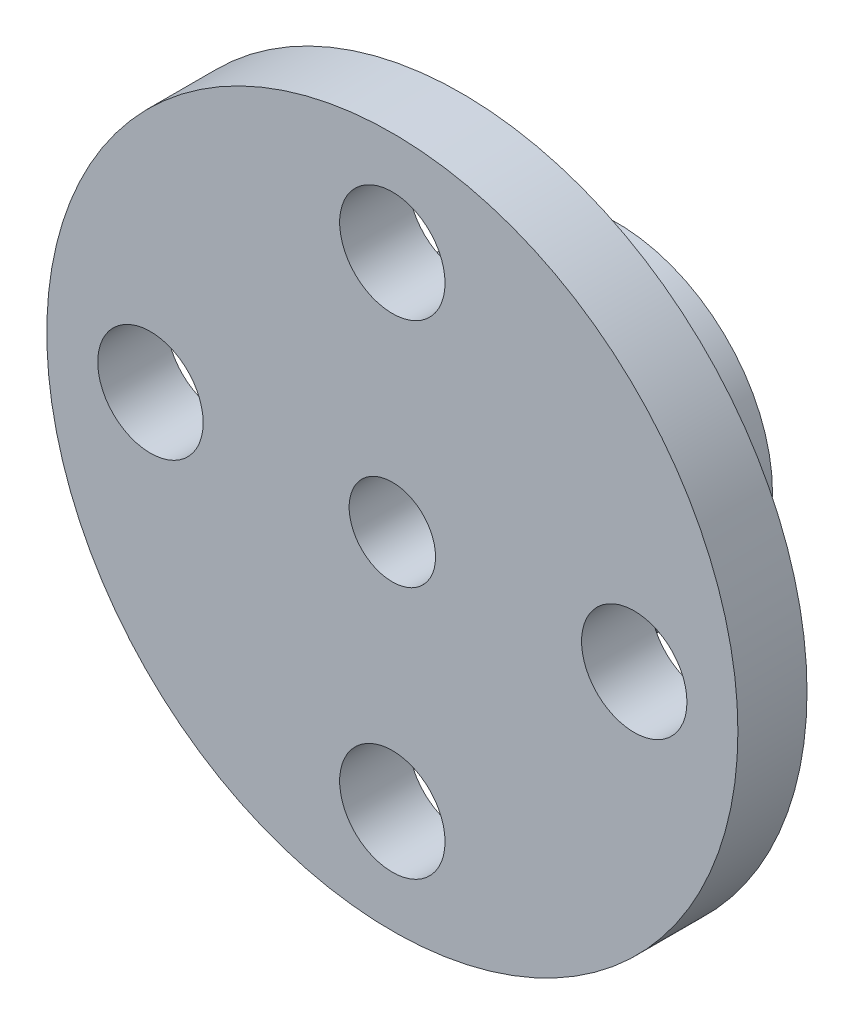
SolidWorks part; units mm, degrees
ref_plane "Front Plane" through (0, 0, 0) normal (0, 0, 1) x (1, 0, 0)
ref_plane "Top Plane" through (0, 0, 0) normal (0, 1, 0) x (1, 0, 0)
ref_plane "Right Plane" through (0, 0, 0) normal (1, 0, 0) x (0, 0, -1)
sketch "Sketch1" plane through (0, 0, 7) normal (0, 0, 1) x (1, 0, 0)
  line L0 (-1.3378, 2.3147) -> (-1.7435, 2.5633)
  line L1 (-1.8991, 2.4502) -> (-1.788, 1.9876)
  line L2 (-1.8714, 1.9093) -> (-2.3261, 2.0492)
  line L3 (-2.4487, 1.901) -> (-2.2261, 1.4805)
  line L4 (-2.2874, 1.3839) -> (-2.7627, 1.4063)
  line L5 (-2.8446, 1.2323) -> (-2.5244, 0.8804)
  line L6 (-2.5597, 0.7715) -> (-3.0256, 0.6751)
  line L7 (-3.0616, 0.4861) -> (-2.664, 0.2249)
  line L8 (-2.6712, 0.1107) -> (-3.0984, -0.0986)
  line L9 (-3.0864, -0.2905) -> (-2.6362, -0.4446)
  line L10 (-2.6148, -0.5571) -> (-2.9766, -0.866)
  line L11 (-2.9171, -1.0489) -> (-2.4428, -1.0863)
  line L12 (-2.3941, -1.1898) -> (-2.6677, -1.5791)
  line L13 (-2.5646, -1.7415) -> (-2.0959, -1.6597)
  line L14 (-2.023, -1.7478) -> (-2.1912, -2.1929)
  line L15 (-2.051, -2.3245) -> (-1.6174, -2.1288)
  line L16 (-1.5248, -2.196) -> (-1.577, -2.6689)
  line L17 (-1.4085, -2.7616) -> (-1.0371, -2.4641)
  line L18 (-0.9307, -2.5062) -> (-0.8637, -2.9772)
  line L19 (-0.6774, -3.0251) -> (-0.3918, -2.6446)
  line L20 (-0.2782, -2.659) -> (-0.0962, -3.0985)
  line L21 (0.0962, -3.0985) -> (0.2782, -2.659)
  line L22 (0.3918, -2.6446) -> (0.6774, -3.0251)
  line L23 (0.8637, -2.9772) -> (0.9307, -2.5062)
  line L24 (1.0371, -2.4641) -> (1.4085, -2.7616)
  line L25 (1.577, -2.6689) -> (1.5248, -2.196)
  line L26 (1.6174, -2.1288) -> (2.051, -2.3245)
  line L27 (2.1912, -2.1929) -> (2.023, -1.7478)
  line L28 (2.0959, -1.6597) -> (2.5646, -1.7415)
  line L29 (2.6677, -1.5791) -> (2.3941, -1.1898)
  line L30 (2.4428, -1.0863) -> (2.9171, -1.0489)
  line L31 (2.9766, -0.866) -> (2.6148, -0.5571)
  line L32 (2.6362, -0.4446) -> (3.0864, -0.2905)
  line L33 (3.0984, -0.0986) -> (2.6712, 0.1107)
  line L34 (2.664, 0.2249) -> (3.0616, 0.4861)
  line L35 (3.0256, 0.6751) -> (2.5597, 0.7715)
  line L36 (2.5244, 0.8804) -> (2.8446, 1.2323)
  line L37 (2.7627, 1.4063) -> (2.2874, 1.3839)
  line L38 (2.2261, 1.4805) -> (2.4487, 1.901)
  line L39 (2.3261, 2.0492) -> (1.8714, 1.9093)
  line L40 (1.788, 1.9876) -> (1.8991, 2.4502)
  line L41 (1.7435, 2.5633) -> (1.3378, 2.3147)
  line L42 (1.2375, 2.3698) -> (1.23, 2.8455)
  line L43 (1.0512, 2.9163) -> (0.7201, 2.5747)
  line L44 (0.6093, 2.6031) -> (0.4837, 3.062)
  line L45 (0.2929, 3.0861) -> (0.0572, 2.6729)
  line L46 (-0.0572, 2.6729) -> (-0.2929, 3.0861)
  line L47 (-0.4837, 3.062) -> (-0.6093, 2.6031)
  line L48 (-0.7201, 2.5747) -> (-1.0512, 2.9163)
  line L49 (-1.23, 2.8455) -> (-1.2375, 2.3698)
  line L150 (-1.8428, 2.4303) -> (-1.7394, 1.9993) construction
  line L151 (-1.3639, 2.272) -> (-1.7419, 2.5037) construction
  line L152 (-1.8861, 1.8615) -> (-2.3098, 1.9918) construction
  line L153 (-2.3893, 1.8957) -> (-2.1819, 1.5039) construction
  line L154 (-2.2898, 1.3339) -> (-2.7326, 1.3548) construction
  line L155 (-2.7857, 1.2419) -> (-2.4874, 0.914) construction
  line L156 (-3.007, 0.5101) -> (-2.6365, 0.2667) construction
  line L157 (-2.5496, 0.7226) -> (-2.9837, 0.6327) construction
  line L158 (-3.0394, -0.2537) -> (-2.62, -0.3973) construction
  line L159 (-2.6492, 0.0658) -> (-3.0473, -0.1292) construction
  line L160 (-2.8808, -1.0016) -> (-2.4389, -1.0364) construction
  line L161 (-2.5823, -0.5951) -> (-2.9194, -0.883) construction
  line L162 (-2.5412, -1.6866) -> (-2.1045, -1.6104) construction
  line L163 (-2.3532, -1.2186) -> (-2.6081, -1.5812) construction
  line L164 (-2.0419, -2.2656) -> (-1.6379, -2.0832) construction
  line L165 (-1.9762, -1.7655) -> (-2.1329, -2.1802) construction
  line L166 (-1.4144, -2.7022) -> (-1.0684, -2.4251) construction
  line L167 (-1.4751, -2.2015) -> (-1.5237, -2.6421) construction
  line L168 (-0.6979, -2.9691) -> (-0.4318, -2.6146) construction
  line L169 (-0.8812, -2.4992) -> (-0.8188, -2.938) construction
  line L170 (0.0624, -3.0494) -> (0.232, -2.6398) construction
  line L171 (-0.232, -2.6398) -> (-0.0624, -3.0494) construction
  line L172 (0.8188, -2.938) -> (0.8812, -2.4992) construction
  line L173 (0.4318, -2.6146) -> (0.6979, -2.9691) construction
  line L174 (1.0684, -2.4251) -> (1.4144, -2.7022) construction
  line L175 (1.5237, -2.6421) -> (1.4751, -2.2015) construction
  line L176 (1.6379, -2.0832) -> (2.0419, -2.2656) construction
  line L177 (2.1329, -2.1802) -> (1.9762, -1.7655) construction
  line L178 (2.1045, -1.6104) -> (2.5412, -1.6866) construction
  line L179 (2.6081, -1.5812) -> (2.3532, -1.2186) construction
  line L180 (2.4389, -1.0364) -> (2.8808, -1.0016) construction
  line L181 (2.9194, -0.883) -> (2.5823, -0.5951) construction
  line L182 (3.0473, -0.1292) -> (2.6492, 0.0658) construction
  line L183 (2.62, -0.3973) -> (3.0394, -0.2537) construction
  line L184 (2.9837, 0.6327) -> (2.5496, 0.7226) construction
  line L185 (2.6365, 0.2667) -> (3.007, 0.5101) construction
  line L186 (2.7326, 1.3548) -> (2.2898, 1.3339) construction
  line L187 (2.4874, 0.914) -> (2.7857, 1.2419) construction
  line L188 (2.3098, 1.9918) -> (1.8861, 1.8615) construction
  line L189 (2.1819, 1.5039) -> (2.3893, 1.8957) construction
  line L190 (1.7394, 1.9993) -> (1.8428, 2.4303) construction
  line L191 (1.7419, 2.5037) -> (1.3639, 2.272) construction
  line L192 (1.0645, 2.8582) -> (0.756, 2.5399) construction
  line L193 (1.1875, 2.369) -> (1.1806, 2.8123) construction
  line L194 (0.5611, 2.5899) -> (0.4441, 3.0175) construction
  line L195 (0.3203, 3.0331) -> (0.1007, 2.6481) construction
  line L196 (-0.4441, 3.0175) -> (-0.5611, 2.5899) construction
  line L197 (-0.1007, 2.6481) -> (-0.3203, 3.0331) construction
  line L198 (-1.1806, 2.8123) -> (-1.1875, 2.369) construction
  line L199 (-0.756, 2.5399) -> (-1.0645, 2.8582) construction
  line L200 (-1.8428, 2.4303) -> (-1.7394, 1.9993) construction
  line L201 (-1.3639, 2.272) -> (-1.7419, 2.5037) construction
  line L202 (-1.8861, 1.8615) -> (-2.3098, 1.9918) construction
  line L203 (-2.3893, 1.8957) -> (-2.1819, 1.5039) construction
  line L204 (-2.2898, 1.3339) -> (-2.7326, 1.3548) construction
  line L205 (-2.7857, 1.2419) -> (-2.4874, 0.914) construction
  line L206 (-3.007, 0.5101) -> (-2.6365, 0.2667) construction
  line L207 (-2.5496, 0.7226) -> (-2.9837, 0.6327) construction
  line L208 (-3.0394, -0.2537) -> (-2.62, -0.3973) construction
  line L209 (-2.6492, 0.0658) -> (-3.0473, -0.1292) construction
  line L210 (-2.8808, -1.0016) -> (-2.4389, -1.0364) construction
  line L211 (-2.5823, -0.5951) -> (-2.9194, -0.883) construction
  line L212 (-2.5412, -1.6866) -> (-2.1045, -1.6104) construction
  line L213 (-2.3532, -1.2186) -> (-2.6081, -1.5812) construction
  line L214 (-2.0419, -2.2656) -> (-1.6379, -2.0832) construction
  line L215 (-1.9762, -1.7655) -> (-2.1329, -2.1802) construction
  line L216 (-1.4144, -2.7022) -> (-1.0684, -2.4251) construction
  line L217 (-1.4751, -2.2015) -> (-1.5237, -2.6421) construction
  line L218 (-0.6979, -2.9691) -> (-0.4318, -2.6146) construction
  line L219 (-0.8812, -2.4992) -> (-0.8188, -2.938) construction
  line L220 (0.0624, -3.0494) -> (0.232, -2.6398) construction
  line L221 (-0.232, -2.6398) -> (-0.0624, -3.0494) construction
  line L222 (0.8188, -2.938) -> (0.8812, -2.4992) construction
  line L223 (0.4318, -2.6146) -> (0.6979, -2.9691) construction
  line L224 (1.0684, -2.4251) -> (1.4144, -2.7022) construction
  line L225 (1.5237, -2.6421) -> (1.4751, -2.2015) construction
  line L226 (1.6379, -2.0832) -> (2.0419, -2.2656) construction
  line L227 (2.1329, -2.1802) -> (1.9762, -1.7655) construction
  line L228 (2.1045, -1.6104) -> (2.5412, -1.6866) construction
  line L229 (2.6081, -1.5812) -> (2.3532, -1.2186) construction
  line L230 (2.4389, -1.0364) -> (2.8808, -1.0016) construction
  line L231 (2.9194, -0.883) -> (2.5823, -0.5951) construction
  line L232 (3.0473, -0.1292) -> (2.6492, 0.0658) construction
  line L233 (2.62, -0.3973) -> (3.0394, -0.2537) construction
  line L234 (2.9837, 0.6327) -> (2.5496, 0.7226) construction
  line L235 (2.6365, 0.2667) -> (3.007, 0.5101) construction
  line L236 (2.7326, 1.3548) -> (2.2898, 1.3339) construction
  line L237 (2.4874, 0.914) -> (2.7857, 1.2419) construction
  line L238 (2.3098, 1.9918) -> (1.8861, 1.8615) construction
  line L239 (2.1819, 1.5039) -> (2.3893, 1.8957) construction
  line L240 (1.7394, 1.9993) -> (1.8428, 2.4303) construction
  line L241 (1.7419, 2.5037) -> (1.3639, 2.272) construction
  line L242 (1.0645, 2.8582) -> (0.756, 2.5399) construction
  line L243 (1.1875, 2.369) -> (1.1806, 2.8123) construction
  line L244 (0.5611, 2.5899) -> (0.4441, 3.0175) construction
  line L245 (0.3203, 3.0331) -> (0.1007, 2.6481) construction
  line L246 (-0.4441, 3.0175) -> (-0.5611, 2.5899) construction
  line L247 (-0.1007, 2.6481) -> (-0.3203, 3.0331) construction
  line L248 (-1.1806, 2.8123) -> (-1.1875, 2.369) construction
  line L249 (-0.756, 2.5399) -> (-1.0645, 2.8582) construction
  arc A0 (-1.7435, 2.5633) -> (-1.8991, 2.4502) centre (0, 0) ccw
  arc A1 (-2.3261, 2.0492) -> (-2.4487, 1.901) centre (0, 0) ccw
  arc A2 (-2.7627, 1.4063) -> (-2.8446, 1.2323) centre (0, 0) ccw
  arc A3 (-3.0256, 0.6751) -> (-3.0616, 0.4861) centre (0, 0) ccw
  arc A4 (-3.0984, -0.0986) -> (-3.0864, -0.2905) centre (0, 0) ccw
  arc A5 (-2.9766, -0.866) -> (-2.9171, -1.0489) centre (0, 0) ccw
  arc A6 (-2.6677, -1.5791) -> (-2.5646, -1.7415) centre (0, 0) ccw
  arc A7 (-2.1912, -2.1929) -> (-2.051, -2.3245) centre (0, 0) ccw
  arc A8 (-1.577, -2.6689) -> (-1.4085, -2.7616) centre (0, 0) ccw
  arc A9 (-0.8637, -2.9772) -> (-0.6774, -3.0251) centre (0, 0) ccw
  arc A10 (-0.0962, -3.0985) -> (0.0962, -3.0985) centre (0, 0) ccw
  arc A11 (0.6774, -3.0251) -> (0.8637, -2.9772) centre (0, 0) ccw
  arc A12 (1.4085, -2.7616) -> (1.577, -2.6689) centre (0, 0) ccw
  arc A13 (2.051, -2.3245) -> (2.1912, -2.1929) centre (0, 0) ccw
  arc A14 (2.5646, -1.7415) -> (2.6677, -1.5791) centre (0, 0) ccw
  arc A15 (2.9171, -1.0489) -> (2.9766, -0.866) centre (0, 0) ccw
  arc A16 (3.0864, -0.2905) -> (3.0984, -0.0986) centre (0, 0) ccw
  arc A17 (3.0616, 0.4861) -> (3.0256, 0.6751) centre (0, 0) ccw
  arc A18 (2.8446, 1.2323) -> (2.7627, 1.4063) centre (0, 0) ccw
  arc A19 (2.4487, 1.901) -> (2.3261, 2.0492) centre (0, 0) ccw
  arc A20 (1.8991, 2.4502) -> (1.7435, 2.5633) centre (0, 0) ccw
  arc A21 (1.23, 2.8455) -> (1.0512, 2.9163) centre (0, 0) ccw
  arc A22 (0.4837, 3.062) -> (0.2929, 3.0861) centre (0, 0) ccw
  arc A23 (-0.2929, 3.0861) -> (-0.4837, 3.062) centre (0, 0) ccw
  arc A24 (-1.0512, 2.9163) -> (-1.23, 2.8455) centre (0, 0) ccw
  circle A25 centre (0, 0) radius 2.6735
  circle A152 centre (0, 0) radius 4.5
  arc A154 (-1.7419, 2.5037) -> (-1.8428, 2.4303) centre (0, 0) ccw construction
  arc A155 (-2.3098, 1.9918) -> (-2.3893, 1.8957) centre (0, 0) ccw construction
  arc A157 (-2.7326, 1.3548) -> (-2.7857, 1.2419) centre (0, 0) ccw construction
  arc A160 (-2.9837, 0.6327) -> (-3.007, 0.5101) centre (0, 0) ccw construction
  arc A162 (-3.0473, -0.1292) -> (-3.0394, -0.2537) centre (0, 0) ccw construction
  arc A165 (-2.9194, -0.883) -> (-2.8808, -1.0016) centre (0, 0) ccw construction
  arc A167 (-2.6081, -1.5812) -> (-2.5412, -1.6866) centre (0, 0) ccw construction
  arc A169 (-2.1329, -2.1802) -> (-2.0419, -2.2656) centre (0, 0) ccw construction
  arc A171 (-1.5237, -2.6421) -> (-1.4144, -2.7022) centre (0, 0) ccw construction
  arc A173 (-0.8188, -2.938) -> (-0.6979, -2.9691) centre (0, 0) ccw construction
  arc A175 (-0.0624, -3.0494) -> (0.0624, -3.0494) centre (0, 0) ccw construction
  arc A177 (0.6979, -2.9691) -> (0.8188, -2.938) centre (0, 0) ccw construction
  arc A178 (1.4144, -2.7022) -> (1.5237, -2.6421) centre (0, 0) ccw construction
  arc A180 (2.0419, -2.2656) -> (2.1329, -2.1802) centre (0, 0) ccw construction
  arc A182 (2.5412, -1.6866) -> (2.6081, -1.5812) centre (0, 0) ccw construction
  arc A184 (2.8808, -1.0016) -> (2.9194, -0.883) centre (0, 0) ccw construction
  arc A187 (3.0394, -0.2537) -> (3.0473, -0.1292) centre (0, 0) ccw construction
  arc A189 (3.007, 0.5101) -> (2.9837, 0.6327) centre (0, 0) ccw construction
  arc A191 (2.7857, 1.2419) -> (2.7326, 1.3548) centre (0, 0) ccw construction
  arc A193 (2.3893, 1.8957) -> (2.3098, 1.9918) centre (0, 0) ccw construction
  arc A194 (1.8428, 2.4303) -> (1.7419, 2.5037) centre (0, 0) ccw construction
  arc A197 (1.1806, 2.8123) -> (1.0645, 2.8582) centre (0, 0) ccw construction
  arc A198 (0.4441, 3.0175) -> (0.3203, 3.0331) centre (0, 0) ccw construction
  arc A201 (-0.3203, 3.0331) -> (-0.4441, 3.0175) centre (0, 0) ccw construction
  arc A203 (-1.0645, 2.8582) -> (-1.1806, 2.8123) centre (0, 0) ccw construction
  arc A205 (-1.7419, 2.5037) -> (-1.8428, 2.4303) centre (0, 0) ccw construction
  arc A206 (-2.3098, 1.9918) -> (-2.3893, 1.8957) centre (0, 0) ccw construction
  arc A208 (-2.7326, 1.3548) -> (-2.7857, 1.2419) centre (0, 0) ccw construction
  arc A211 (-2.9837, 0.6327) -> (-3.007, 0.5101) centre (0, 0) ccw construction
  arc A213 (-3.0473, -0.1292) -> (-3.0394, -0.2537) centre (0, 0) ccw construction
  arc A215 (-2.9194, -0.883) -> (-2.8808, -1.0016) centre (0, 0) ccw construction
  arc A217 (-2.6081, -1.5812) -> (-2.5412, -1.6866) centre (0, 0) ccw construction
  arc A219 (-2.1329, -2.1802) -> (-2.0419, -2.2656) centre (0, 0) ccw construction
  arc A221 (-1.5237, -2.6421) -> (-1.4144, -2.7022) centre (0, 0) ccw construction
  arc A223 (-0.8188, -2.938) -> (-0.6979, -2.9691) centre (0, 0) ccw construction
  arc A225 (-0.0624, -3.0494) -> (0.0624, -3.0494) centre (0, 0) ccw construction
  arc A227 (0.6979, -2.9691) -> (0.8188, -2.938) centre (0, 0) ccw construction
  arc A228 (1.4144, -2.7022) -> (1.5237, -2.6421) centre (0, 0) ccw construction
  arc A230 (2.0419, -2.2656) -> (2.1329, -2.1802) centre (0, 0) ccw construction
  arc A232 (2.5412, -1.6866) -> (2.6081, -1.5812) centre (0, 0) ccw construction
  arc A234 (2.8808, -1.0016) -> (2.9194, -0.883) centre (0, 0) ccw construction
  arc A237 (3.0394, -0.2537) -> (3.0473, -0.1292) centre (0, 0) ccw construction
  arc A239 (3.007, 0.5101) -> (2.9837, 0.6327) centre (0, 0) ccw construction
  arc A241 (2.7857, 1.2419) -> (2.7326, 1.3548) centre (0, 0) ccw construction
  arc A243 (2.3893, 1.8957) -> (2.3098, 1.9918) centre (0, 0) ccw construction
  arc A244 (1.8428, 2.4303) -> (1.7419, 2.5037) centre (0, 0) ccw construction
  arc A247 (1.1806, 2.8123) -> (1.0645, 2.8582) centre (0, 0) ccw construction
  arc A248 (0.4441, 3.0175) -> (0.3203, 3.0331) centre (0, 0) ccw construction
  arc A251 (-0.3203, 3.0331) -> (-0.4441, 3.0175) centre (0, 0) ccw construction
  arc A253 (-1.0645, 2.8582) -> (-1.1806, 2.8123) centre (0, 0) ccw construction
  dimension "D2" = 9
  dimension "D1" = 0.05
extrude "Boss-Extrude1" add sketch "Sketch1" against normal blind 6.5 contours A152 A25 L33 A16 L32 L31 A15 L30 L29 A14 L28 L27 A13 L26 L25 A12 L24 L23 A11 L22 L21 A10 L20 L19 A9 L18 L17 A8 L16 L15 A7 L14 L13 A6 L12 L11 A5 L10 region at (-4.3727, 0, 7)
sketch "Sketch2" plane through (0, 0, 7) normal (0, 0, 1) x (1, 0, 0)
  circle A2 centre (0, 0) radius 10
  circle A4 centre (0, 0) radius 1.25 construction
  circle A5 centre (0, 0) radius 1.25
  dimension "D1" = 20
extrude "Boss-Extrude2" add sketch "Sketch2" against normal blind 2
sketch "Sketch3" plane through (0, 0, 7) normal (0, 0, 1) x (1, 0, 0)
  line L0 (0, 10) -> (0, -49990) construction
  line L1 (0, 0) -> (50000, 0) construction
  circle A6 centre (0, 7) radius 1.525
  circle A8 centre (7, 0) radius 1.525
  circle A9 centre (0, -7) radius 1.525
  circle A10 centre (-7, 0) radius 1.525
  point P8 (-2.4939, 0.501)
  point P9 (0, 0)
  point P17 (0, 0)
  dimension "D1" = 3.05
  dimension "D2" = 4
  dimension "D3" = 7
extrude "Cut-Extrude1" cut sketch "Sketch3" against normal through all
